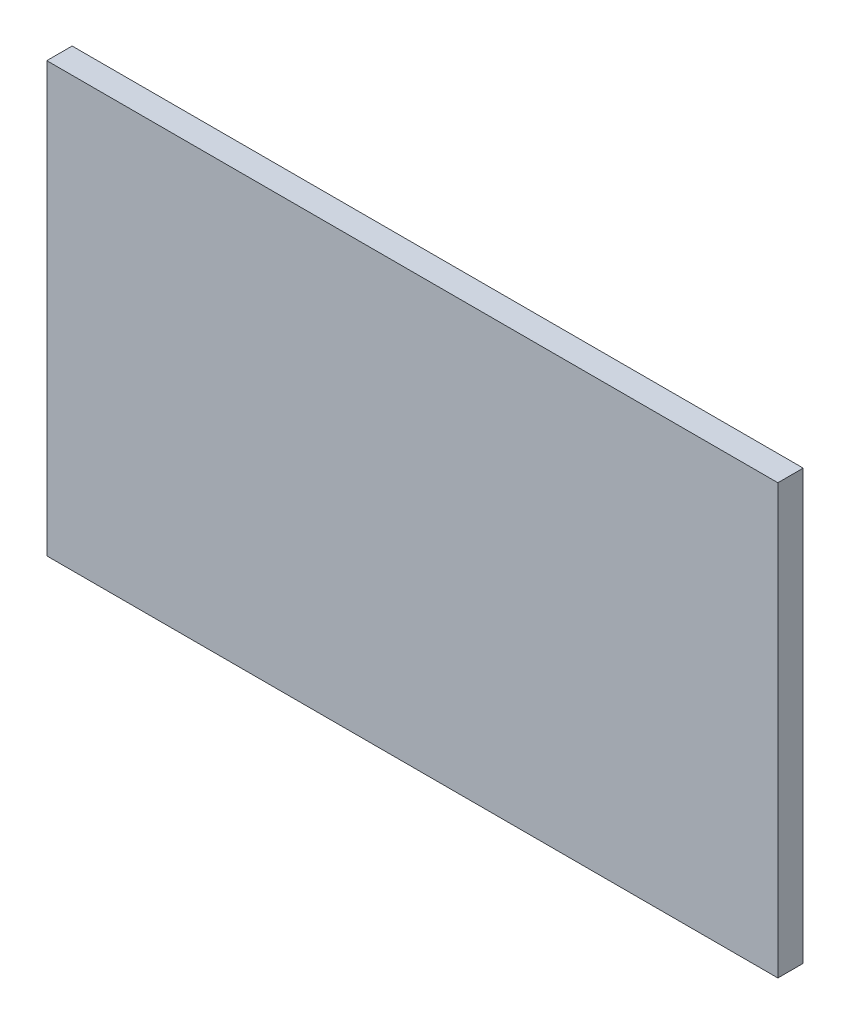
SolidWorks part; units mm, degrees
ref_plane "Plan de face" through (0, 0, 0) normal (0, 0, 1) x (1, 0, 0)
ref_plane "Plan de dessus" through (0, 0, 0) normal (0, 1, 0) x (1, 0, 0)
ref_plane "Plan de droite" through (0, 0, 0) normal (1, 0, 0) x (0, 0, -1)
sketch "Esquisse2" plane through (0, 0, 0) normal (0, 0, 1) x (1, 0, 0)
  line L1 (0, 0) -> (3750, 0)
  line L2 (0, 0) -> (0, 2200)
  line L3 (0, 2200) -> (3750, 2200)
  line L4 (3750, 0) -> (3750, 2200)
  dimension "D1" = 3750
  dimension "D2" = 2200
extrude "Boss.-Extru.1" add sketch "Esquisse2" against normal blind 130 contours L3 L4 L1 L2
